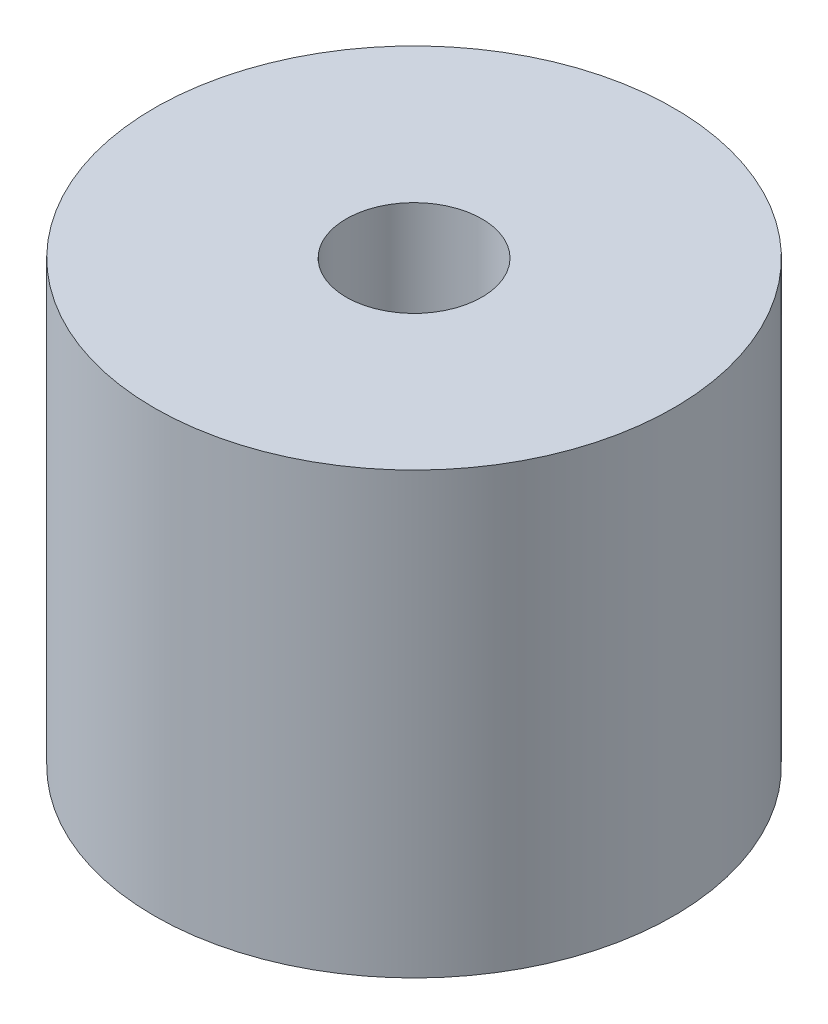
SolidWorks part; units mm, degrees
material "PTFE (general)"
ref_plane "Front Plane" through (0, 0, 0) normal (0, 0, 1) x (1, 0, 0)
ref_plane "Top Plane" through (0, 0, 0) normal (0, 1, 0) x (1, 0, 0)
ref_plane "Right Plane" through (0, 0, 0) normal (1, 0, 0) x (0, 0, -1)
sketch "Sketch1" plane through (0, 0, 0) normal (0, 1, 0) x (1, 0, 0)
  circle A0 centre (0, 0) radius 9.525
  dimension "D1" = 19.05
extrude "Boss-Extrude1" add sketch "Sketch1" along normal blind 16.129
hole_wizard "#10 Clearance Hole1" positions "Sketch2" profile "Sketch3" hole size "#10" standard "ANSI Inch" end condition through all
sketch "Sketch2" plane through (0, 16.129, 0) normal (0, 1, 0) x (1, 0, 0)
  point P0 (0, 0)
sketch "Sketch3" plane through (0, 16.129, 0) normal (1, 0, 0) x (0, 0, 1)
  line L0 (0, 0) -> (0, 16.129)
  line L1 (0, 16.129) -> (2.4892, 16.129)
  line L2 (2.4892, 16.129) -> (2.4892, 0)
  line L5 (2.4892, 0) -> (0, 0)
  line L11 (0, -6.35) -> (0, 107.95) construction
  dimension "Thru Hole Dia." = 4.9784
  dimension "Thru Hole Depth" = 16.129
